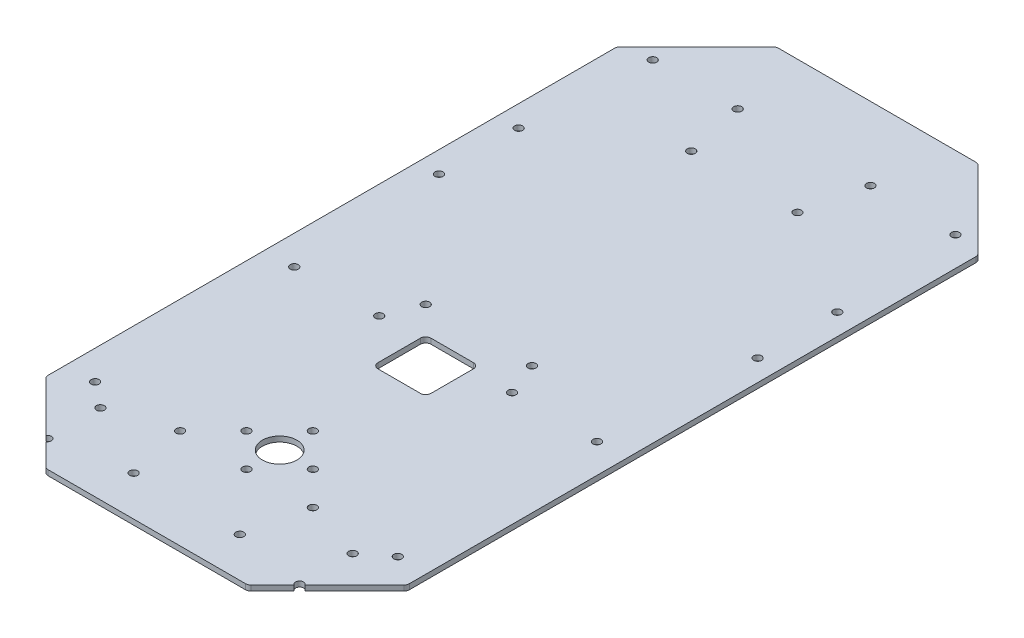
SolidWorks part; units mm, degrees
ref_plane "Спереди" through (0, 0, 0) normal (0, 0, 1) x (1, 0, 0)
ref_plane "Сверху" through (0, 0, 0) normal (0, 1, 0) x (1, 0, 0)
ref_plane "Справа" through (0, 0, 0) normal (1, 0, 0) x (0, 0, -1)
sketch "компоновка" plane through (0, 0, 0) normal (0, 1, 0) x (1, 0, 0)
  line L0 (-31.5, -17) -> (31.5, 77) construction
  line L1 (-31.5, -17) -> (31.5, -17) construction
  line L2 (-31.5, -17) -> (-31.5, 77) construction
  line L3 (-31.5, 77) -> (31.5, 77) construction
  line L4 (31.5, -17) -> (31.5, 77) construction
  line L5 (-20, 80) -> (20, -20) construction
  line L6 (-20, 80) -> (20, 80) construction
  line L7 (-20, 80) -> (-20, -20) construction
  line L8 (-20, -20) -> (20, -20) construction
  line L9 (20, 80) -> (20, -20) construction
  circle A0 centre (-20, 80) radius 1.5
  circle A1 centre (20, 80) radius 1.5
  circle A2 centre (20, -20) radius 1.5
  circle A3 centre (-20, -20) radius 1.5
  point P4 (0, 30)
  point P14 (0, 30)
  dimension "D3" = 3
  dimension "D1" = 63
  dimension "D2" = 94
  dimension "D4" = 40
  dimension "D5" = 100
  dimension "D6" = 30
sketch "Эскиз1" plane through (0, 0, 0) normal (0, 1, 0) x (1, 0, 0)
  line L0 (0, 130) -> (0, -145) construction
  line L1 (-68, 130) -> (68, 130)
  line L2 (-68, 130) -> (-68, -145)
  line L3 (-68, -145) -> (68, -145)
  line L4 (68, 130) -> (68, -145)
  line L5 (-68, 0) -> (68, 0) construction
  dimension "D1" = 136
  dimension "D2" = 130
  dimension "D3" = 145
extrude "тело" add sketch "Эскиз1" along normal blind 2
sketch "Эскиз12" plane through (0, 2, 0) normal (0, 1, 0) x (1, 0, 0)
  line L0 (0, 130) -> (0, -145) construction
  line L1 (68, 130) -> (-68, 130) construction
  line L2 (-68, -145) -> (68, -145) construction
  line L3 (60, 55) -> (60, 25) construction
  line L4 (60, 40) -> (-60, 40) construction
  line L5 (-60, 55) -> (-60, 25) construction
  circle A0 centre (60, 55) radius 1.5
  circle A1 centre (-60, 55) radius 1.5
  circle A2 centre (-60, 25) radius 1.5
  circle A3 centre (60, 25) radius 1.5
  point P12 (-60, 40)
  point P17 (0, 40)
  dimension "D2" = 3
  dimension "D1" = 30
  dimension "D3" = 60
  dimension "D4" = 40
extrude "крепление подвески" cut sketch "Эскиз12" against normal through all
sketch "Эскиз5" plane through (0, 2, 0) normal (0, 1, 0) x (1, 0, 0)
  circle A0 centre (-20, 80) radius 1.5
  circle A1 centre (20, 80) radius 1.5
  circle A2 centre (20, -20) radius 1.5
  circle A3 centre (-20, -20) radius 1.5
  dimension "D1" = 3
extrude "крепление raspberry" cut sketch "Эскиз5" against normal through all
sketch "Эскиз8" plane through (0, 2, 0) normal (0, 1, 0) x (1, 0, 0)
  line L0 (-20, -130) -> (20, -130) construction
  line L1 (0, -145) -> (0, 130) construction
  line L2 (-68, -145) -> (68, -145) construction
  line L3 (68, 130) -> (-68, 130) construction
  circle A0 centre (-20, -130) radius 1.5
  circle A1 centre (20, -130) radius 1.5
  point P10 (0, -130)
  dimension "D1" = 3
  dimension "D2" = 40
  dimension "D3" = 130
extrude "крепление камеры" cut sketch "Эскиз8" against normal through all and the other way through all
sketch "Эскиз11" plane through (0, 2, 0) normal (0, 1, 0) x (1, 0, 0)
  line L0 (-10, -40) -> (10, -40) construction
  line L1 (-10, -30) -> (10, -30)
  line L2 (-10, -30) -> (-10, -50)
  line L3 (-10, -50) -> (10, -50)
  line L4 (10, -30) -> (10, -50)
  point P6 (0, -40)
  dimension "D1" = 20
  dimension "D2" = 20
  dimension "D3" = 40
extrude "отверстие для шлейфа камеры" cut sketch "Эскиз11" against normal through all
sketch "Эскиз13" plane through (0, 2, 0) normal (0, 1, 0) x (1, 0, 0)
  line L0 (0, 130) -> (0, -145) construction
  line L1 (68, 130) -> (-68, 130) construction
  line L2 (-68, -145) -> (68, -145) construction
  line L3 (-57, 102.5) -> (57, 102.5) construction
  line L4 (-68, -7.5) -> (68, -7.5) construction
  line L5 (-57, -32.5) -> (57, -32.5) construction
  line L6 (-68, 130) -> (-68, -145) construction
  line L7 (-57, -107.5) -> (57, -107.5) construction
  line L8 (68, -145) -> (68, 130) construction
  line L9 (-25, 102.5) -> (-57, 102.5) construction
  line L10 (25, 102.5) -> (57, 102.5) construction
  line L11 (-57, -32.5) -> (-25, -32.5) construction
  line L12 (25, -32.5) -> (57, -32.5) construction
  line L13 (-57, -107.5) -> (-25, -107.5) construction
  line L14 (25, -107.5) -> (57, -107.5) construction
  circle A0 centre (-57, 102.5) radius 1.5
  circle A1 centre (57, 102.5) radius 1.5
  circle A2 centre (57, -32.5) radius 1.5
  circle A3 centre (-57, -32.5) radius 1.5
  circle A4 centre (-57, -107.5) radius 1.5
  circle A5 centre (57, -107.5) radius 1.5
  circle A6 centre (-25, 102.5) radius 1.5
  circle A7 centre (25, 102.5) radius 1.5
  circle A8 centre (25, -32.5) radius 1.5
  circle A9 centre (-25, -32.5) radius 1.5
  circle A10 centre (-25, -107.5) radius 1.5
  circle A11 centre (25, -107.5) radius 1.5
  point P18 (0, 102.5)
  point P19 (0, -32.5)
  point P20 (0, -107.5)
  point P27 (0, -7.5)
  dimension "D1" = 3
  dimension "D2" = 110
  dimension "D3" = 25
  dimension "D4" = 100
  dimension "D5" = 114
  dimension "D6" = 32
  dimension "D7" = 32
  dimension "D8" = 32
  dimension "D9" = 32
  dimension "D10" = 32
  dimension "D11" = 32
extrude "крепления уголков" cut sketch "Эскиз13" against normal through all
sketch "Эскиз9" plane through (0, 2, 0) normal (0, 1, 0) x (1, 0, 0)
  line L1 (-68, -145) -> (68, -145) construction
  circle A0 centre (0, -95) radius 6.5
  circle A1 centre (0, -95) radius 12.5 construction
  circle A2 centre (0, -82.5) radius 1.5
  circle A3 centre (12.5, -95) radius 1.5
  circle A4 centre (-12.5, -95) radius 1.5
  circle A5 centre (0, -107.5) radius 1.5
  dimension "D2" = 13
  dimension "D3" = 25
  dimension "D4" = 3
  dimension "D1" = 50
extrude "ось вращения качалки" cut sketch "Эскиз9" against normal through all
fillet "Скругление3" radius 2 4 edges at (-10, 1, 50) (10, 1, 50) (10, 1, 30) (-10, 1, 30)
chamfer "Фаска1" distance 30 angle 45 4 edges at (-68, 1, 145) (68, 1, 145) (68, 1, -130) (-68, 1, -130)
sketch "Эскиз14" plane through (0, 2, 0) normal (0, 1, 0) x (1, 0, 0)
  line L0 (0, 130) -> (0, -145) construction
  line L1 (38, 130) -> (-38, 130) construction
  line L2 (-38, -145) -> (38, -145) construction
  line L3 (-47.5, -125) -> (47.5, -125) construction
  line L4 (47.5, -115) -> (47.5, -135) construction
  line L5 (-12.5, -95) -> (12.5, -95) construction
  line L6 (-47.5, -115) -> (-47.5, -135) construction
  circle A0 centre (-47.5, -115) radius 1.5
  circle A1 centre (-47.5, -135) radius 1.5
  circle A2 centre (47.5, -115) radius 1.5
  circle A3 centre (47.5, -135) radius 1.5
  point P8 (0, -125)
  point P14 (-47.5, -125)
  point P15 (47.5, -125)
  dimension "D1" = 3
  dimension "D2" = 20
  dimension "D3" = 30
  dimension "D4" = 95
extrude "крепление стопоров" cut sketch "Эскиз14" against normal through all
fillet "Скругление4" radius 2 8 edges at (-68, 1, -100) (-38, 1, -130) (38, 1, -130) (68, 1, -100) (68, 1, 115) (38, 1, 145) (-68, 1, 115) (-38, 1, 145)
